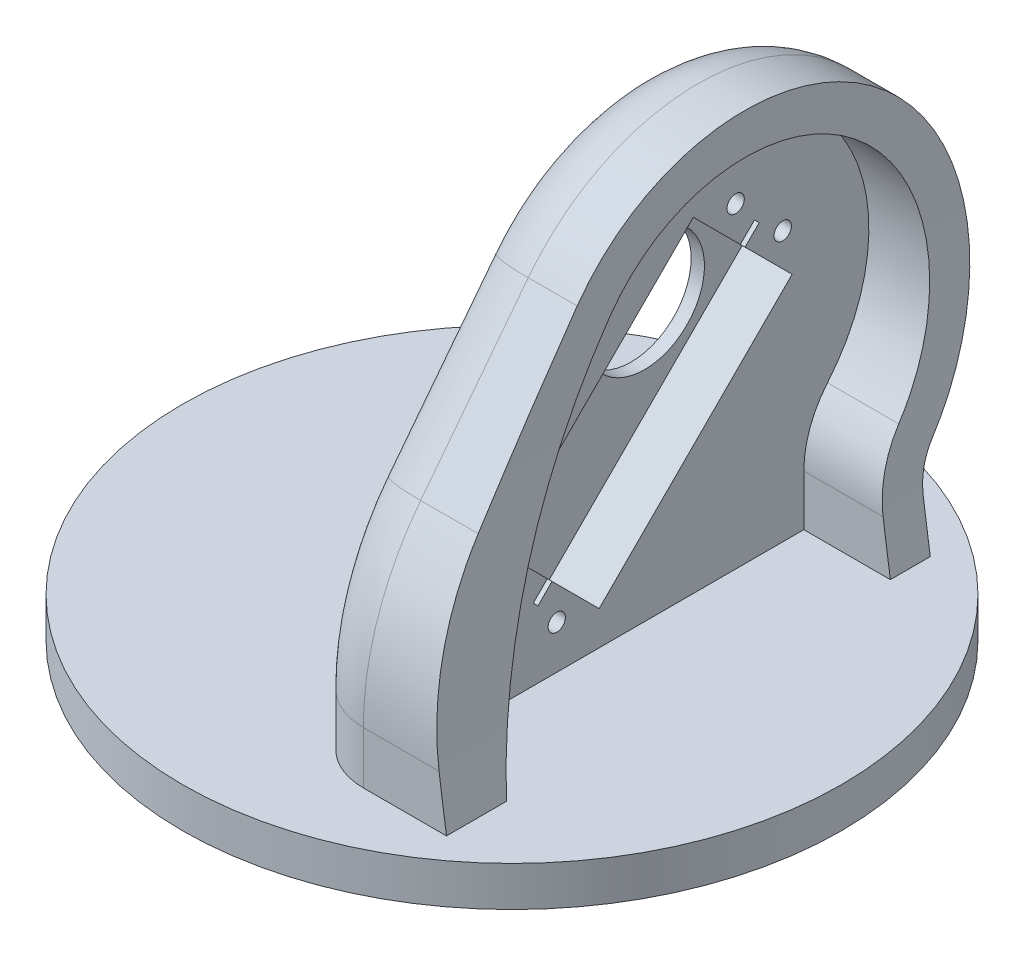
SolidWorks part; units mm, degrees
ref_plane "Front Plane" through (0, 0, 0) normal (0, 0, 1) x (1, 0, 0)
ref_plane "Top Plane" through (0, 0, 0) normal (0, 1, 0) x (1, 0, 0)
ref_plane "Right Plane" through (0, 0, 0) normal (1, 0, 0) x (0, 0, -1)
sketch "Sketch1" plane through (0, 0, 0) normal (0, 1, 0) x (1, 0, 0)
  circle A0 centre (0, 0) radius 49.5
  dimension "D1" = 99
extrude "Boss-Extrude1" add sketch "Sketch1" along normal blind 6
sketch "Sketch3" plane through (0, 0, 0) normal (1, 0, 0) x (0, 0, -1)
  line L0 (30.34, 6) -> (-30.34, 6)
  line L1 (49.5, 6) -> (-49.5, 6) construction
  line L2 (30.34, 6) -> (30.34, 13.64)
  line L3 (-30.34, 6) -> (-30.34, 13.86)
  line L4 (-22.9773, 35.4137) -> (-6.8154, 56.3099)
  arc A0 (30.34, 13.64) -> (33.8974, 23.3388) centre (45.34, 13.64) cw
  arc A1 (33.8974, 23.3388) -> (-6.8154, 56.3099) centre (13.91, 40.28) ccw
  arc A2 (-30.34, 13.86) -> (-22.9773, 35.4137) centre (4.89, 13.86) cw
  circle A3 centre (13.91, 40.28) radius 9
  point P5 (0, 6)
  dimension "D3" = 15
  dimension "D5" = 35.23
  dimension "D6" = 18
  dimension "D1" = 60.68
  dimension "D2" = 7.64
  dimension "D4" = 7.86
  dimension "D7" = 13.91
  dimension "D8" = 40.28
extrude "Boss-Extrude2" add sketch "Sketch3" along normal blind 14 from offset 4
sketch "Sketch4" plane through (0, 0, 0) normal (0, -1, 0) x (1, 0, 0)
  line L3 (-3.375, 24) -> (-3.375, 12.0244)
  line L4 (3.375, 24) -> (3.375, 12.0244)
  arc A0 (-5.912, 4.4921) -> (5.912, 4.4921) centre (0, 0) ccw
  circle A3 centre (0, 0) radius 49.5 construction
  arc A4 (-0.0086, 20) -> (0.0084, 20) centre (0, 24) ccw
  arc A7 (3.375, 24) -> (-3.375, 24) centre (0, 24) ccw
  arc A8 (5.912, 4.4921) -> (3.375, 12.0244) centre (15.825, 12.0244) cw
  arc A9 (-5.912, 4.4921) -> (-3.375, 12.0244) centre (-15.825, 12.0244) ccw
  circle A10 centre (0, 24) radius 1.5
  circle A11 centre (0.0084, 20) radius 1.5
  point P1 (0, 27.375)
  point P6 (0, 0)
  point P13 (-0.0084, 7.425)
  point P19 (0.0084, 7.425)
  point P21 (0, -7.425)
  dimension "D1" = 7.425
  dimension "D4" = 3
  dimension "D6" = 34.8
  dimension "D2" = 12.45
  dimension "D3" = 3.375
  dimension "D8" = 3
  dimension "D5" = 4
  dimension "D7" = 6.75
extrude "Cut-Extrude2" cut sketch "Sketch4" against normal blind 4 contours A9 A0 A8 L4 A7 L3 A11 A10 region at (-0.0002, 0, 6.6061)
sketch "Sketch5" plane through (0, 0, 0) normal (1, 0, 0) x (0, 0, -1)
  line L0 (-0.41, 11.11) -> (28.5814, 40.1014)
  line L1 (-0.41, 11.11) -> (-15.2592, 25.9592)
  line L2 (28.5814, 40.1014) -> (13.7321, 54.9506)
  line L3 (-15.2592, 25.9592) -> (13.7321, 54.9506)
  line L4 (-49.5, 0) -> (49.5, 0) construction
  line L5 (-30.34, 6) -> (30.34, 6) construction
  line L6 (14.0857, 25.6057) -> (-0.7636, 40.4549) construction
  line L7 (6.6611, 33.0303) -> (23.6316, 50.0009) construction
  line L8 (27.1672, 46.4653) -> (20.0961, 53.5364) construction
  circle A0 centre (27.1672, 46.4653) radius 1.3
  circle A1 centre (20.0961, 53.5364) radius 1.3
  circle A2 centre (-13.845, 19.5953) radius 1.3
  circle A3 centre (-6.774, 12.5242) radius 1.3
  point P16 (23.6316, 50.0009)
  dimension "D8" = 2.6
  dimension "D1" = 0.41
  dimension "D2" = 11.11
  dimension "D3" = 21
  dimension "D4" = 41
  dimension "D5" = 45
  dimension "D6" = 3.5
  dimension "D7" = 10
extrude "Cut-Extrude3" cut sketch "Sketch5" along normal through all from offset 6
sketch "Sketch6" plane through (18, 0, 0) normal (1, 0, 0) x (0, 0, -1)
  line L0 (-6.8154, 56.3099) -> (-22.9773, 35.4137) construction
  line L1 (-6.8154, 56.3099) -> (-22.9773, 35.4137)
  line L2 (-30.34, 13.86) -> (-30.34, 6) construction
  line L3 (-30.34, 13.86) -> (-30.34, 6)
  line L4 (30.34, 6) -> (30.34, 13.64) construction
  line L5 (30.34, 6) -> (30.34, 13.64)
  line L6 (33.34, 6) -> (33.34, 13.64) construction
  line L7 (-9.1885, 58.1453) -> (-25.3504, 37.2491) construction
  line L8 (-33.34, 13.86) -> (-33.34, 6) construction
  line L9 (36.34, 6) -> (36.34, 13.64)
  line L10 (-11.5615, 59.9807) -> (-27.7234, 39.0846)
  line L11 (-36.34, 13.86) -> (-36.34, 6)
  line L12 (-30.34, 6) -> (30.34, 6) construction
  line L13 (-36.34, 6) -> (-27.34, 6)
  line L14 (30.34, 6) -> (36.34, 6)
  arc A0 (33.8974, 23.3388) -> (-6.8154, 56.3099) centre (13.91, 40.28) ccw construction
  arc A1 (33.8974, 23.3388) -> (-6.8154, 56.3099) centre (13.91, 40.28) ccw
  arc A2 (-22.9773, 35.4137) -> (-30.34, 13.86) centre (4.89, 13.86) ccw construction
  arc A3 (-22.9773, 35.4137) -> (-30.34, 13.86) centre (4.89, 13.86) ccw
  arc A4 (33.8974, 23.3388) -> (30.34, 13.64) centre (45.34, 13.64) ccw construction
  arc A5 (33.8974, 23.3388) -> (30.34, 13.64) centre (45.34, 13.64) ccw
  arc A6 (36.1859, 21.399) -> (33.34, 13.64) centre (45.34, 13.64) ccw construction
  arc A7 (36.1859, 21.399) -> (-9.1885, 58.1453) centre (13.91, 40.28) ccw construction
  arc A8 (-25.3504, 37.2491) -> (-33.34, 13.86) centre (4.89, 13.86) ccw construction
  arc A9 (38.4744, 19.4593) -> (36.34, 13.64) centre (45.34, 13.64) ccw
  arc A10 (38.4744, 19.4593) -> (-11.5615, 59.9807) centre (13.91, 40.28) ccw
  arc A11 (-27.7234, 39.0846) -> (-36.34, 13.86) centre (4.89, 13.86) ccw
  arc A12 (-6.8154, 56.3099) -> (-27.34, 6) centre (72.031, -5.1981) ccw
  line M4 (-30.34, 13.86) -> (-30.34, 6)
  line M5 (-30.34, 6) -> (30.34, 6)
  line M6 (30.34, 6) -> (30.34, 13.64)
  arc M7 (30.34, 13.64) -> (33.8974, 23.3388) centre (45.34, 13.64) cw
  arc M8 (33.8974, 23.3388) -> (-6.8154, 56.3099) centre (13.91, 40.28) ccw
  arc M10 (-22.9773, 35.4137) -> (-30.34, 13.86) centre (4.89, 13.86) ccw
  dimension "D4" = 100
  dimension "D3" = 3
  dimension "D1" = 3
  dimension "D2" = 3
extrude "Boss-Extrude3" add sketch "Sketch6" along normal blind 9 and the other way up to surface (14 mm away) contours A12 L14 L9 A9 A10 L10 A11 L11 L13 L1 M8 M7 M6 M4 M10 | A12 L1 M10 M4 M5 region at (18, 56.6299, 7.9079) region at (18, 24.5941, 24.8971) other way up to face at (4, 25.1867, -2.616)
sketch "Sketch7" plane through (0, 0, 0) normal (0, 0, 1) x (1, 0, 0)
  line L0 (27, 72.4811) -> (21, 72.4811)
  line L3 (27, 72.4811) -> (4, 72.4811) construction
  line L4 (49.5, 6) -> (-49.5, 6) construction
  line L5 (26.5, 6) -> (27, 6)
  arc A0 (21, 72.4811) -> (26.5, 6) centre (520.9377, 80.373) ccw
  dimension "D3" = 0.5
  dimension "D2" = 6
  dimension "D1" = 500
extrude "Cut-Extrude4" cut sketch "Sketch7" against normal through all both and the other way through all
fillet "Fillet1" radius 10 6 edges at (4, 9.82, -36.34) (4, 16.7392, -36.8904) (4, 9.93, 36.34) (4, 27.1878, 34.1264) (4, 49.5326, 19.6425) (4, 65.3042, -34.1758)
extrude "Cut-Extrude5" cut sketch "Sketch4<3>" against normal blind 10 contours A10 | A11
sketch "Sketch4<3>" plane through (0, 0, 0) normal (0, -1, 0) x (1, 0, 0) same geometry as "Sketch4"
sketch "Sketch8" plane through (18, 0, 0) normal (1, 0, 0) x (0, 0, -1)
  line L0 (-14.7073, 11.6619) -> (25.6048, 51.9741) construction
  line L1 (-0.7636, 40.4549) -> (14.0857, 25.6057) construction
  line L2 (13.7321, 54.9506) -> (-15.2592, 25.9592) construction
  line L3 (-0.41, 11.11) -> (28.5814, 40.1014) construction
  line L4 (-8.1882, 18.8882) -> (-7.4811, 18.1811)
  line L5 (-7.4811, 18.1811) -> (-9.6024, 16.0597)
  line L6 (-15.2592, 25.9592) -> (-0.41, 11.11) construction
  line L8 (-9.6024, 16.0597) -> (-10.3095, 16.7669)
  line L9 (-10.3095, 16.7669) -> (-8.1882, 18.8882)
  line L10 (22.9245, 50.0009) -> (20.8032, 47.8796)
  line L11 (23.6316, 49.2938) -> (22.9245, 50.0009)
  line L12 (21.5103, 47.1724) -> (23.6316, 49.2938)
  line L13 (20.8032, 47.8796) -> (21.5103, 47.1724)
  dimension "D1" = 0.5
  dimension "D2" = 0.5
  dimension "D3" = 3
extrude "Cut-Extrude6" cut sketch "Sketch8" against normal blind 8.5
sketch "Sketch9" plane through (18, 0, 0) normal (1, 0, 0) x (0, 0, -1)
  line L0 (-27.34, 6) -> (30.34, 6) construction
  line L1 (30.34, 13.64) -> (30.34, 6) construction
  line L2 (-27.34, 6) -> (30.34, 6)
  line L3 (30.34, 13.64) -> (30.34, 6)
  line L4 (-6.8154, 56.3099) -> (-7.3235, 55.6529) construction
  line L5 (-6.8154, 56.3099) -> (-7.3235, 55.6529)
  arc A0 (33.8974, 23.3388) -> (30.34, 13.64) centre (45.34, 13.64) ccw construction
  arc A1 (33.8974, 23.3388) -> (-6.8154, 56.3099) centre (13.91, 40.28) ccw construction
  arc A2 (-7.3235, 55.6529) -> (-27.34, 6) centre (72.031, -5.1981) ccw construction
  arc A3 (33.8974, 23.3388) -> (30.34, 13.64) centre (45.34, 13.64) ccw
  arc A4 (33.8974, 23.3388) -> (-6.8154, 56.3099) centre (13.91, 40.28) ccw
  arc A5 (-7.3235, 55.6529) -> (-27.34, 6) centre (72.031, -5.1981) ccw
extrude "Cut-Extrude8" cut sketch "Sketch9" against normal blind 4.5
